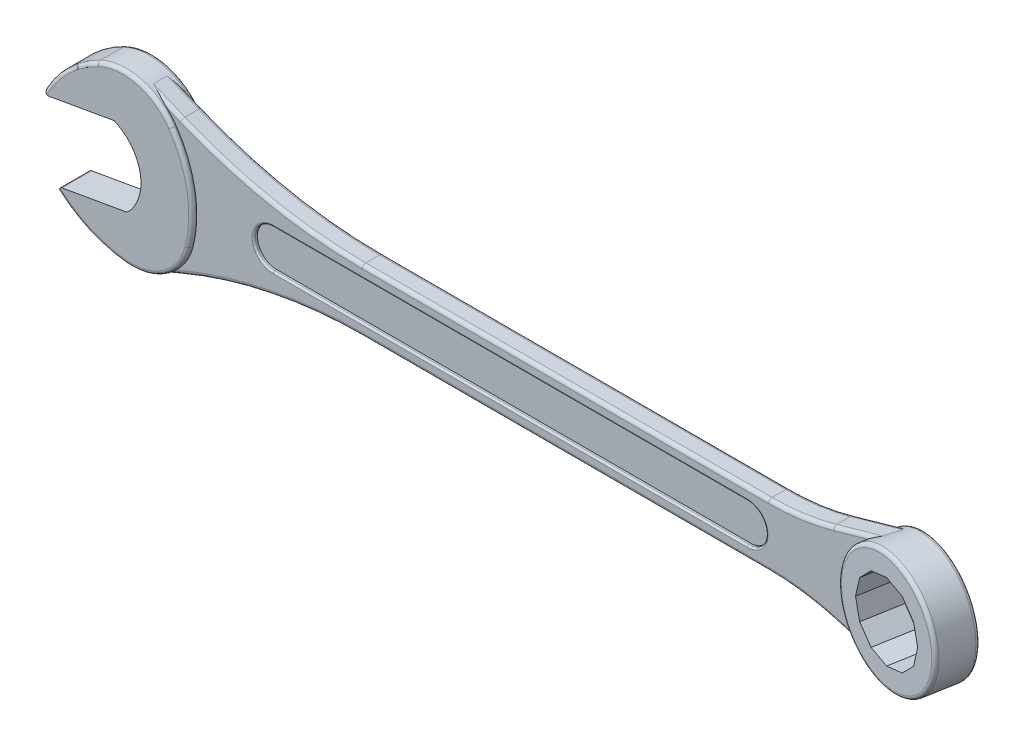
SolidWorks part; units mm, degrees
material "Alloy Steel"
ref_plane "Front Plane" through (0, 0, 0) normal (0, 0, 1) x (1, 0, 0)
ref_plane "Top Plane" through (0, 0, 0) normal (0, 1, 0) x (1, 0, 0)
ref_plane "Right Plane" through (0, 0, 0) normal (1, 0, 0) x (0, 0, -1)
sketch "Sketch1" plane through (0, 0, 0) normal (0, 0, 1) x (1, 0, 0)
  line L0 (-20.5248, 0) -> (261.6311, 0) construction
  line L3 (-16.836, 5.0854) -> (-1.3773, 7.8112)
  line L4 (1.3773, -7.8112) -> (-1.3773, 7.8112) construction
  line L5 (-14.0814, -10.537) -> (1.3773, -7.8112)
  line L6 (0, 0) -> (-21.2363, -3.7445) construction
  line L7 (0, 0) -> (4.2274, 0.7454) construction
  line L8 (164.0694, 12.065) -> (164.0694, -12.065)
  line L21 (120.5531, -6.6675) -> (120.5531, 6.6675) construction
  line L22 (50.8562, 6.6675) -> (137.9616, 6.6675)
  line L23 (151.8098, 8.5915) -> (164.0694, 12.065)
  line L24 (51.3583, -6.6675) -> (137.9616, -6.6675)
  line L25 (12.1048, 14.3479) -> (5.3194, 17.1476)
  line L26 (11.7163, -14.7203) -> (7.2516, -16.6123)
  line L27 (164.0694, -12.065) -> (151.8098, -8.5915)
  arc A7 (-1.3773, 7.8112) -> (1.3773, -7.8112) centre (-5.1029, -0.8998) cw
  arc A8 (-16.836, 5.0854) -> (-5.0541, 16.8407) centre (6.0049, -6.0254) cw
  arc A9 (-5.0541, 16.8407) -> (10.9565, 12.5796) centre (0.4754, 5.4077) cw
  arc A10 (10.9565, 12.5796) -> (14.5983, -8.0736) centre (-10.0056, -1.7643) cw
  arc A11 (-14.0814, -10.537) -> (1.0106, -17.5537) centre (3.582, 7.7158) ccw
  arc A12 (1.0106, -17.5537) -> (14.5983, -8.0736) centre (2.2963, -4.9189) ccw
  arc A14 (50.8562, 6.6675) -> (12.1048, 14.3479) centre (50.8562, 108.2675) cw
  arc A15 (51.3583, -6.6675) -> (11.7163, -14.7203) centre (51.3583, -108.2675) ccw
  arc A16 (151.8098, 8.5915) -> (137.9616, 6.6675) centre (137.9616, 57.4675) cw
  arc A17 (151.8098, -8.5915) -> (137.9616, -6.6675) centre (137.9616, -57.4675) ccw
  point P8 (0, 0)
  point P25 (164.0694, 0)
  point P27 (120.5531, 0)
  point P35 (30.7194, 6.6675)
  point P39 (145.0194, 6.6675)
  point P42 (145.0194, -6.6675)
  point P44 (30.7194, -6.6675)
  dimension "D1" = 5.1816
  dimension "D2" = 9.4742
  dimension "D3" = 10
  dimension "D4" = 25.4
  dimension "D5" = 12.7
  dimension "D6" = 25.4
  dimension "D11" = 24.13
  dimension "D14" = 101.6
  dimension "D15" = 101.6
  dimension "D16" = 50.8
  dimension "D17" = 50.8
  dimension "D7" = 10.16
  dimension "D8" = 15.6972
  dimension "D9" = 34.925
  dimension "D10" = 15.8634
  dimension "D12" = 158.75
  dimension "D13" = 13.335
  dimension "D18" = 19.05
  dimension "D19" = 25.4
ref_plane "Plane2" through (4.9473, 0, -28.0575) normal (-0.1736, 0, 0.9848) x (0, -1, 0)
sketch "Sketch8" plane through (4.9473, 0, -28.0575) normal (-0.1736, 0, 0.9848) x (0, -1, 0)
  line L0 (0, -20.213) -> (0, 257.6564) construction
  line L2 (8.2175, 165.1) -> (7.1166, 169.2088)
  line L3 (7.1166, 169.2088) -> (4.1088, 172.2166)
  line L4 (4.1088, 172.2166) -> (0, 173.3175)
  line L5 (0, 173.3175) -> (-4.1088, 172.2166)
  line L6 (-4.1088, 172.2166) -> (-7.1166, 169.2088)
  line L7 (-7.1166, 169.2088) -> (-8.2175, 165.1)
  line L8 (-8.2175, 165.1) -> (-7.1166, 160.9912)
  line L9 (-7.1166, 160.9912) -> (-4.1088, 157.9834)
  line L10 (-4.1088, 157.9834) -> (0, 156.8825)
  line L11 (0, 156.8825) -> (4.1088, 157.9834)
  line L12 (4.1088, 157.9834) -> (7.1166, 160.9912)
  line L13 (7.1166, 160.9912) -> (8.2175, 165.1)
  circle A0 centre (0, 165.1) radius 12.7
  circle A1 centre (0, 165.1) radius 7.9375 construction
  dimension "D2" = 25.4
  dimension "D1" = 165.1
  dimension "D3" = 7.9375
extrude "Boss-Extrude8" add sketch "Sketch1" along normal mid plane 6.35 contours A11 A12 A10 A9 A8 L3 A7 L5 region at (-11.5954, 11.6148, 0)
extrude "Boss-Extrude9" add sketch "Sketch1<16>" along normal mid plane 4.445 contours A17 L27 L8 L23 A16 L22 A14 L25 A9 A10 A12 L26 A15 L24 region at (87.0038, 0.0453, 0)
sketch "Sketch1<16>" plane through (0, 0, 0) normal (0, 0, 1) x (1, 0, 0) same geometry as "Sketch1"
extrude "Boss-Extrude10" add sketch "Sketch8" along normal blind 5.08 and the other way blind 3.302
sketch "Sketch10" plane through (4.0652, 0, -23.0547) normal (-0.1736, 0, 0.9848) x (0.9848, 0, 0.1736)
  line L0 (165.1, 8.2175) -> (165.1, -8.2175) construction
  line L2 (165.1, 8.2175) -> (160.9912, 7.1166)
  line L3 (160.9912, 7.1166) -> (157.9834, 4.1088)
  line L4 (157.9834, 4.1088) -> (156.8825, 0)
  line L5 (156.8825, 0) -> (157.9834, -4.1088)
  line L6 (157.9834, -4.1088) -> (160.9912, -7.1166)
  line L7 (160.9912, -7.1166) -> (165.1, -8.2175)
  line L8 (165.1, -8.2175) -> (169.2088, -7.1166)
  line L9 (169.2088, -7.1166) -> (172.2166, -4.1088)
  line L10 (172.2166, -4.1088) -> (173.3175, 0)
  line L11 (173.3175, 0) -> (172.2166, 4.1088)
  line L12 (172.2166, 4.1088) -> (169.2088, 7.1166)
  line L13 (169.2088, 7.1166) -> (165.1, 8.2175)
  circle A0 centre (165.1, 0) radius 7.9375 construction
extrude "Cut-Extrude2" cut sketch "Sketch10" against normal blind 8.382
sketch "Sketch12" plane through (0, 0, 2.2225) normal (0, 0, 1) x (1, 0, 0)
  line L0 (31.75, 0) -> (133.35, 0) construction
  line L1 (-20.5248, 0) -> (261.6311, 0) construction
  line L2 (31.75, 4.1275) -> (133.35, 4.1275)
  line L3 (31.75, -4.1275) -> (133.35, -4.1275)
  arc A0 (31.75, 4.1275) -> (31.75, -4.1275) centre (31.75, 0) ccw
  arc A1 (133.35, -4.1275) -> (133.35, 4.1275) centre (133.35, 0) ccw
  point P4 (82.55, 0)
  dimension "D1" = 31.75
  dimension "D2" = 101.6
  dimension "D3" = 8.255
extrude "Cut-Extrude3" cut sketch "Sketch12" against normal blind 0.762
fillet "Fillet1" radius 0.762 34 edges at (157.7603, -10.2774, -2.2225) (144.9522, -7.1508, -2.2225) (94.66, -6.6675, -2.2225) (9.4839, -15.6663, -2.2225) (-11.9352, 11.9555, -3.175) (3.7418, 17.6805, -3.175) (15.0085, 2.6464, -3.175) (9.5632, -15.3344, -3.175) (8.7121, 15.7478, -2.2225) (31.1036, 8.6061, -2.2225) (157.7603, 10.2774, -2.2225) (144.9522, 7.1508, -2.2225) (156.5893, -9.9456, 2.2225) (144.9522, -7.1508, 2.2225) (94.66, -6.6675, 2.2225) (9.4839, -15.6663, 2.2225) (156.5893, 9.9456, 2.2225) (144.9522, 7.1508, 2.2225) (94.4089, 6.6675, 2.2225) (8.7121, 15.7478, 2.2225) (-7.1264, -15.3165, 3.175) (9.5632, -15.3344, 3.175) (15.0085, 2.6464, 3.175) (3.7418, 17.6805, 3.175) (-16.836, 5.0854, 0) (31.1325, -8.7011, -2.2225) (-7.1264, -15.3165, -3.175) (-14.0814, -10.537, 0) (94.4089, 6.6675, -2.2225) (180.6195, 0, -0.4347) (179.164, 0, 7.82) (31.1325, -8.7011, 2.2225) (31.1036, 8.6061, 2.2225) (-11.9352, 11.9555, 3.175)
fillet "Fillet2" radius 0.381 4 edges at (137.4775, 0, 2.2225) (82.55, -4.1275, 2.2225) (27.6225, 0, 2.2225) (82.55, 4.1275, 2.2225)
mirror "Mirror2" about plane through (0, 0, 0) normal (0, 0, 1) of "Cut-Extrude3"
